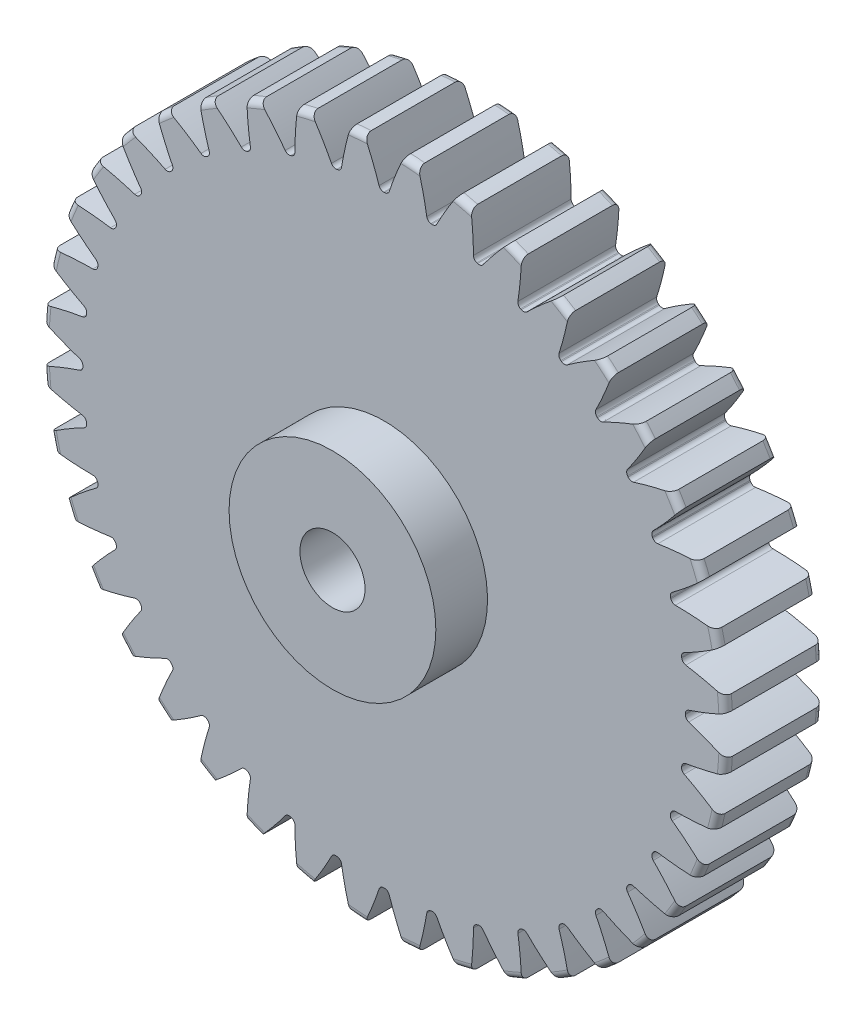
SolidWorks part; units mm, degrees
ref_plane "Front Plane" through (0, 0, 0) normal (0, 0, 1) x (1, 0, 0)
ref_plane "Top Plane" through (0, 0, 0) normal (0, 1, 0) x (1, 0, 0)
ref_plane "Right Plane" through (0, 0, 0) normal (1, 0, 0) x (0, 0, -1)
sketch "Sketch1" plane through (0, 0, 0) normal (0, 0, 1) x (1, 0, 0)
  line L0 (-508, 0) -> (508, 0) construction
  circle A0 centre (0, 0) radius 21 construction
  circle A1 centre (0, 0) radius 20 construction
  circle A2 centre (0, 0) radius 18.5 construction
  circle A3 centre (0, 0) radius 8 construction
  circle A4 centre (0, 0) radius 4 construction
  dimension "D2" = 1
  dimension "D3" = 2.5
  dimension "D1" = 2.5
sketch "Sketch2" plane through (0, 0, 0) normal (1, 0, 0) x (0, 0, -1)
  line L0 (0, 0) -> (-6, 0) construction
  line L1 (-6, 0) -> (-12, 0) construction
  dimension "Overall Width" = 12
  dimension "Face Width" = 6
sketch "Sketch4" plane through (0, 0, 0) normal (1, 0, 0) x (0, 0, -1)
  line L0 (-12, 4) -> (-12, 8)
  line L1 (-12, 8) -> (-6, 8)
  line L2 (-6, 8) -> (-6, 21)
  line L3 (-6, 21) -> (0, 21)
  line L4 (0, 21) -> (0, 4)
  line L5 (-6, 8) -> (-6, 0) construction
  line L6 (0, 21) -> (0, -21) construction
  line L7 (-6, 8) -> (0, 8) construction
  line L12 (-12, 4) -> (0, 4)
revolve "Revolve1" add sketch "Sketch4" angle 360 about L1
fillet "Fillet2" radius 0.42 4 edges at (0, 8, 12) (0, 8, 6) (0, 21, 6) (0, 21, 0)
sketch "Sketch7" plane through (0, 0, 6) normal (0, 0, 1) x (1, 0, 0)
  line L0 (0, 0) -> (0, 21) construction
  line L1 (0.7852, 19.9846) -> (1.1869, 20.9664) construction
  line L3 (1.6476, 20.9353) -> (1.5692, 19.9383) construction
  line L4 (1.5692, 19.9383) -> (1.4515, 18.443) construction
  line L5 (0, 0) -> (1.4515, 18.443) construction
  line L6 (0.7852, 19.9846) -> (0, 0) construction
  line L7 (0.7852, 19.9846) -> (0.8245, 20.9838) construction
  line L8 (0.7852, 19.9846) -> (0, 0) construction
  circle A0 centre (0, 0) radius 21 construction
  arc A1 (-0.027, 18.5) -> (0.027, 18.5) centre (0, 0) cw
  circle A2 centre (0, 0) radius 18.5 construction
  arc A3 (-0.7852, 19.9846) -> (0.7852, 19.9846) centre (0, 0) cw construction
  circle A4 centre (0, 0) radius 20 construction
  arc A5 (2.0774, 20.897) -> (1.2172, 20.9647) centre (0, 0) ccw construction
  arc A6 (0.7852, 19.9846) -> (2.3507, 19.8614) centre (0, 0) cw construction
  arc A7 (-1.2172, 20.9647) -> (1.2172, 20.9647) centre (0, 0) cw
  arc A8 (0.3122, 18.7056) -> (1.2172, 20.9647) centre (19.296, 12.4116) cw
  arc A9 (-0.3122, 18.7056) -> (-1.2172, 20.9647) centre (-19.296, 12.4116) ccw
  arc A10 (-0.027, 18.5) -> (-0.3122, 18.7056) centre (-0.0274, 18.8) cw
  arc A11 (0.027, 18.5) -> (0.3122, 18.7056) centre (0.0274, 18.8) ccw
  point P26 (-0.2447, 18.4984)
  point P29 (0.2447, 18.4984)
  dimension "D4" = 0.3
  dimension "D5" = 20
  dimension "D3" = 20
  dimension "D1" = 3.1416
  dimension "D2" = 1.5708
extrude "Cut-Extrude2" cut sketch "Sketch7" against normal through all
pattern_circular "CirPattern1" count 40 over 360 about axis through (0, 0, 12) along (0, 0, -1) of "Cut-Extrude2"
sketch "Sketch8" plane through (0, 0, 0) normal (0, 0, -1) x (-1, 0, 0)
  circle A0 centre (0, 0) radius 2
  circle A1 centre (0, 0) radius 4
  circle A2 centre (0, 0) radius 4 construction
  dimension "D1" = 4
extrude "Boss-Extrude1" add sketch "Sketch8" against normal up to surface (12 mm away) up to face at (0, -7.58, 12)
sketch "Sketch9" plane through (0, 0, 12) normal (0, 0, 1) x (1, 0, 0)
  circle A0 centre (0, 0) radius 8.42
  dimension "D1" = 16.84
extrude "Cut-Extrude3" cut sketch "Sketch9" against normal up to surface (6 mm away) up to face at (0, 0, 6)
ref_plane "Plane1" through (0, 0, 3) normal (0, 0, 1) x (1, 0, 0)
sketch "Sketch10" plane through (0, 0, 3) normal (0, 0, 1) x (1, 0, 0)
  circle A0 centre (0, 0) radius 2
  circle A1 centre (0, 0) radius 6.35
  dimension "D1" = 4
  dimension "D2" = 12.7
extrude "Boss-Extrude2" add sketch "Sketch10" along normal mid plane 12.35
equation "\"D1@Sketch1\"=2.5*(\"Pitch Dia.@Sketch1\"/\"Number of Teeth@Sketch1\")"
equation "\"D1@CirPattern1\"=\"Number of Teeth@Sketch1\""
equation "\"D1@Fillet2\"=\"OD@Sketch1\"*.01"
equation "\"D1@Sketch7\"=3.14159*(\"Pitch Dia.@Sketch1\"/\"Number of Teeth@Sketch1\")"
equation "\"D2@Sketch7\"=\"D1@Sketch7\"/2"
equation "\"D4@Sketch7\"=\"D1@Sketch7\"*.0955"
equation "\"D5@Sketch7\"=\"Pitch Dia.@Sketch1\"/2"
